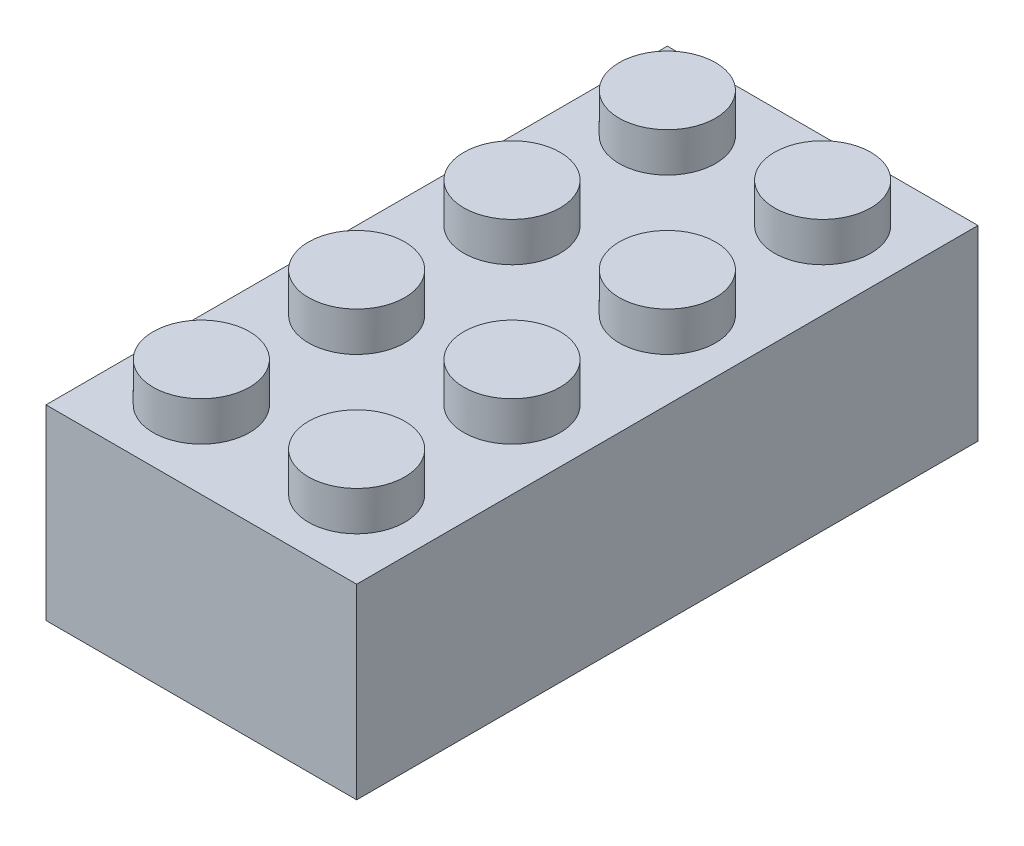
SolidWorks part; units mm, degrees
ref_plane "Front Plane" through (0, 0, 0) normal (0, 0, 1) x (1, 0, 0)
ref_plane "Top Plane" through (0, 0, 0) normal (0, 1, 0) x (1, 0, 0)
ref_plane "Right Plane" through (0, 0, 0) normal (1, 0, 0) x (0, 0, -1)
sketch "stencil" plane through (0, 0, 0) normal (0, 1, 0) x (1, 0, 0)
  line L2 (0, 0) -> (0, 31.6) construction
  line L29 (0, 0) -> (15.8, 0) construction
  line L30 (0, 3.95) -> (15.8, 3.95) construction
  line L31 (0, 7.9) -> (15.8, 7.9) construction
  line L32 (0, 11.85) -> (15.8, 11.85) construction
  line L33 (0, 15.8) -> (15.8, 15.8) construction
  line L34 (0, 19.75) -> (15.8, 19.75) construction
  line L35 (0, 23.7) -> (15.8, 23.7) construction
  line L36 (0, 27.65) -> (15.8, 27.65) construction
  line L37 (0, 31.6) -> (15.8, 31.6) construction
  line L38 (3.95, 0) -> (3.95, 31.6) construction
  line L39 (7.9, 0) -> (7.9, 31.6) construction
  line L40 (11.85, 0) -> (11.85, 31.6) construction
  line L41 (15.8, 0) -> (15.8, 31.6) construction
  line L42 (0, 31.6) -> (0, 0)
  line L43 (0, 0) -> (15.8, 0)
  line L44 (15.8, 0) -> (15.8, 31.6)
  line L45 (15.8, 31.6) -> (0, 31.6)
  circle A26 centre (3.95, 3.95) radius 2.45
  circle A27 centre (11.85, 3.95) radius 2.45
  circle A28 centre (11.85, 11.85) radius 2.45
  circle A29 centre (3.95, 11.85) radius 2.45
  circle A30 centre (11.85, 19.75) radius 2.45
  circle A31 centre (3.95, 19.75) radius 2.45
  circle A32 centre (11.85, 27.65) radius 2.45
  circle A33 centre (3.95, 27.65) radius 2.45
  circle A34 centre (7.9, 7.9) radius 3.25
  circle A35 centre (7.9, 7.9) radius 2.45
  circle A36 centre (7.9, 15.8) radius 2.45
  circle A37 centre (7.9, 15.8) radius 3.25
  circle A38 centre (7.9, 23.7) radius 2.45
  circle A39 centre (7.9, 23.7) radius 3.25
  point P6 (3.95, -15.8)
  point P9 (7.9, -15.8)
  point P10 (7.9, -11.85)
  point P13 (3.95, -7.9)
  point P15 (7.9, -7.9)
  point P17 (7.9, -3.95)
  point P18 (3.95, 0)
  point P21 (7.9, 0)
  point P25 (7.9, 3.95)
  point P27 (3.95, 7.9)
  point P28 (7.9, 7.9)
  point P29 (0, -11.85)
  point P30 (0, -7.9)
  point P31 (0, 3.95)
  point P34 (0, -3.95)
  point P36 (0, 15.8)
  point P37 (0, 23.7)
  point P38 (7.9, 23.7)
  point P39 (15.8, 23.7)
  point P40 (15.8, 15.8)
  point P41 (15.8, 7.9)
  dimension "D7" = 4.9
  dimension "D9" = 6.5
  dimension "D1" = 31.6
  dimension "D2" = 15.8
  dimension "D4" = 3.95
  dimension "D6" = 3.95
  dimension "D8" = 0.8
  dimension "D5" = 9
  dimension "D3" = 5
sketch "Sketch1" plane through (0, 0, 0) normal (0, 1, 0) x (1, 0, 0)
  line L17 (0, 0) -> (15.8, 0)
  line L18 (0, 0) -> (0, 31.6)
  line L19 (0, 31.6) -> (15.8, 31.6)
  line L20 (15.8, 0) -> (15.8, 31.6)
extrude "Boss-Extrude1" add sketch "Sketch1" along normal mid plane 9.5
sketch "Sketch2" plane through (0, 4.75, 0) normal (0, 1, 0) x (1, 0, 0)
  circle A3 centre (3.95, 3.95) radius 2.45
  circle A11 centre (11.85, 3.95) radius 2.45
  circle A12 centre (11.85, 11.85) radius 2.45
  circle A13 centre (3.95, 11.85) radius 2.45
  circle A14 centre (3.95, 19.75) radius 2.45
  circle A15 centre (11.85, 19.75) radius 2.45
  circle A16 centre (3.95, 27.65) radius 2.45
  circle A26 centre (3.95, 27.65) radius 2.45 construction
  circle A27 centre (11.85, 27.65) radius 2.45
extrude "Boss-Extrude2" add sketch "Sketch2" along normal blind 2
sketch "Sketch3" plane through (0, -4.75, 0) normal (0, -1, 0) x (1, 0, 0)
  line L0 (0, -15.8) -> (15.8, -15.8) construction
  line L5 (14.3, -30.1) -> (1.5, -30.1)
  line L7 (14.3, -30.1) -> (14.3, -1.5)
  line L15 (14.3, -1.5) -> (1.5, -1.5)
  line L16 (1.5, -30.1) -> (1.5, -1.5)
  line L17 (7.9, -1.5) -> (7.9, -30.1) construction
  line L18 (14.3, -15.8) -> (1.5, -15.8) construction
  line L19 (0, 0) -> (15.8, 0) construction
  line L20 (0, -31.6) -> (0, 0) construction
  point P0 (7.9, -15.8)
  dimension "D1" = 1.5
  dimension "D2" = 1.5
extrude "Cut-Extrude1" cut sketch "Sketch3" against normal blind 4
sketch "Sketch4" plane through (0, -0.75, 0) normal (0, -1, 0) x (1, 0, 0)
  line L0 (0, -7.9) -> (15.8, -7.9) construction
  line L1 (0, -15.8) -> (15.8, -15.8) construction
  line L2 (0, -23.7) -> (15.8, -23.7) construction
  circle A2 centre (7.9, -7.9) radius 3.25
  circle A3 centre (7.9, -7.9) radius 2.45
  circle A6 centre (7.9, -15.8) radius 3.25
  circle A7 centre (7.9, -15.8) radius 2.45
  circle A10 centre (7.9, -23.7) radius 3.25
  circle A11 centre (7.9, -23.7) radius 2.45
  circle A20 centre (7.9, -23.7) radius 2.45 construction
  circle A21 centre (7.9, -23.7) radius 3.25 construction
extrude "Boss-Extrude3" add sketch "Sketch4" along normal up to surface (4 mm away) up to face at (7.9, -4.75, -15.8)
equation "\"t\"= 0'tolerance"
equation "\"D1@Sketch3\"= 1.5 - \"t\""
equation "\"D2@Sketch3\"=1.5-\"t\""
equation "\"D1@stencil\"=31.60mm-\"t\""
equation "\"D9@stencil\"=6.5-\"t\""
equation "\"D2@stencil\"=15.80-\"t\""
equation "\"D1@Boss-Extrude1\"=9.5-\"t\""
